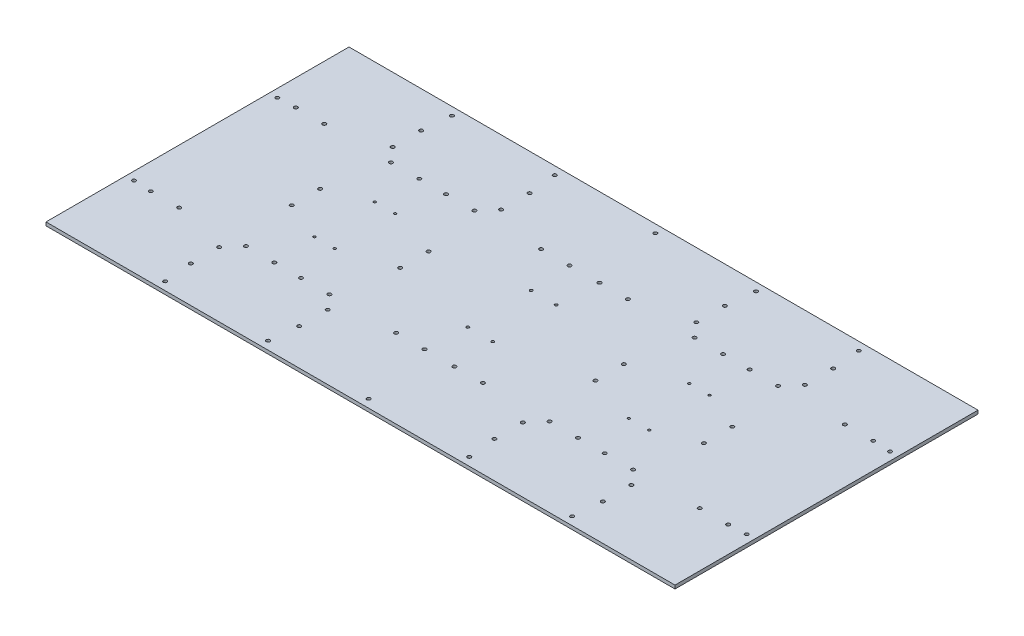
SolidWorks part; units mm, degrees
ref_plane "Front Plane" through (0, 0, 0) normal (0, 0, 1) x (1, 0, 0)
ref_plane "Top Plane" through (0, 0, 0) normal (0, 1, 0) x (1, 0, 0)
ref_plane "Right Plane" through (0, 0, 0) normal (1, 0, 0) x (0, 0, -1)
sketch "Sketch1" plane through (0, 0, 0) normal (0, 1, 0) x (1, 0, 0)
  line L0 (0, 139.7) -> (0, -139.7) construction
  line L1 (-290, 139.7) -> (290, 139.7)
  line L2 (-290, 139.7) -> (-290, -139.7)
  line L3 (-290, -139.7) -> (290, -139.7)
  line L4 (290, 139.7) -> (290, -139.7)
  line L5 (-290, 139.7) -> (290, -139.7) construction
  line L6 (-290, -139.7) -> (290, 139.7) construction
  line L7 (-282.5, 132.2) -> (282.5, 132.2) construction
  line L8 (-282.5, 132.2) -> (-282.5, -132.2) construction
  line L9 (-282.5, -132.2) -> (282.5, -132.2) construction
  line L10 (282.5, 132.2) -> (282.5, -132.2) construction
  line L11 (-282.5, 132.2) -> (282.5, -132.2) construction
  line L12 (-282.5, -132.2) -> (282.5, 132.2) construction
  line L13 (-290, 0) -> (290, 0) construction
  line L14 (282.5, 132.2) -> (282.5, -132.2) construction
  circle A0 centre (-282.5, 66.1) radius 1.65
  circle A1 centre (-187.6333, 132.2) radius 1.65
  circle A2 centre (-92.7667, 132.2) radius 1.65
  circle A3 centre (-282.5, -66.1) radius 1.65
  circle A4 centre (-92.7667, -132.2) radius 1.65
  circle A5 centre (-187.6333, -132.2) radius 1.65
  circle A6 centre (187.6333, -132.2) radius 1.65
  circle A7 centre (92.7667, -132.2) radius 1.65
  circle A8 centre (92.7667, 132.2) radius 1.65
  circle A9 centre (187.6333, 132.2) radius 1.65
  circle A10 centre (282.5, -66.1) radius 1.65
  circle A11 centre (282.5, 66.1) radius 1.65
  circle A12 centre (0, 132.2) radius 1.65
  circle A13 centre (0, -132.2) radius 1.65
  point P0 (0, 0)
  point P6 (0, 0)
  dimension "D5" = 3.3
  dimension "D6" = 3.3
  dimension "D7" = 3.3
  dimension "D12" = 3.3
  dimension "D13" = 3.3
  dimension "D1" = 580
  dimension "D2" = 279.4
  dimension "D3" = 7.5
  dimension "D4" = 7.5
  dimension "D8" = 66.1
  dimension "D9" = 94.8667
  dimension "D10" = 94.8667
  dimension "D11" = 92.7667
extrude "Boss-Extrude1" add sketch "Sketch1" along normal blind 3.175
sketch "Sketch2" plane through (0, 3.175, 0) normal (0, 1, 0) x (1, 0, 0)
  line L0 (0, 139.7) -> (0, -139.7) construction
  line L1 (290, 139.7) -> (-290, 139.7) construction
  line L2 (-290, -139.7) -> (290, -139.7) construction
  line L3 (-140, 139.7) -> (-140, -139.7) construction
  line L5 (-290, 0) -> (290, 0) construction
  line L6 (-290, 139.7) -> (-290, -139.7) construction
  line L7 (290, -139.7) -> (290, 139.7) construction
  line L8 (-190, 139.7) -> (-190, -139.7) construction
  circle A0 centre (-190, 13.1) radius 1.65
  circle A6 centre (-266.2, 66.8739) radius 1.65
  circle A7 centre (-240, 66.8739) radius 1.65
  circle A8 centre (-178.5, 66.8739) radius 1.65
  circle A9 centre (-152.3, 66.8739) radius 1.65
  circle A10 centre (-190, 106.2) radius 1.65
  circle A11 centre (-190, 80) radius 1.65
  circle A12 centre (-190, -80) radius 1.65
  circle A13 centre (-190, -106.2) radius 1.65
  circle A14 centre (-152.3, -66.8739) radius 1.65
  circle A15 centre (-178.5, -66.8739) radius 1.65
  circle A16 centre (-240, -66.8739) radius 1.65
  circle A17 centre (-266.2, -66.8739) radius 1.65
  circle A18 centre (-190, -13.1) radius 1.65
  circle A19 centre (-90, -13.1) radius 1.65
  circle A20 centre (-13.8, -66.8739) radius 1.65
  circle A21 centre (-40, -66.8739) radius 1.65
  circle A22 centre (-101.5, -66.8739) radius 1.65
  circle A23 centre (-127.7, -66.8739) radius 1.65
  circle A24 centre (-90, -106.2) radius 1.65
  circle A25 centre (-90, -80) radius 1.65
  circle A26 centre (-90, 80) radius 1.65
  circle A27 centre (-90, 106.2) radius 1.65
  circle A28 centre (-127.7, 66.8739) radius 1.65
  circle A29 centre (-101.5, 66.8739) radius 1.65
  circle A30 centre (-40, 66.8739) radius 1.65
  circle A31 centre (-13.8, 66.8739) radius 1.65
  circle A32 centre (-90, 13.1) radius 1.65
  circle A33 centre (90, 13.1) radius 1.65
  circle A34 centre (13.8, 66.8739) radius 1.65
  circle A35 centre (40, 66.8739) radius 1.65
  circle A36 centre (101.5, 66.8739) radius 1.65
  circle A37 centre (127.7, 66.8739) radius 1.65
  circle A38 centre (90, 106.2) radius 1.65
  circle A39 centre (90, 80) radius 1.65
  circle A40 centre (90, -80) radius 1.65
  circle A41 centre (90, -106.2) radius 1.65
  circle A42 centre (127.7, -66.8739) radius 1.65
  circle A43 centre (101.5, -66.8739) radius 1.65
  circle A44 centre (40, -66.8739) radius 1.65
  circle A45 centre (13.8, -66.8739) radius 1.65
  circle A46 centre (90, -13.1) radius 1.65
  circle A47 centre (190, -13.1) radius 1.65
  circle A48 centre (266.2, -66.8739) radius 1.65
  circle A49 centre (240, -66.8739) radius 1.65
  circle A50 centre (178.5, -66.8739) radius 1.65
  circle A51 centre (152.3, -66.8739) radius 1.65
  circle A52 centre (190, -106.2) radius 1.65
  circle A53 centre (190, -80) radius 1.65
  circle A54 centre (190, 80) radius 1.65
  circle A55 centre (190, 106.2) radius 1.65
  circle A56 centre (152.3, 66.8739) radius 1.65
  circle A57 centre (178.5, 66.8739) radius 1.65
  circle A58 centre (240, 66.8739) radius 1.65
  circle A59 centre (266.2, 66.8739) radius 1.65
  circle A60 centre (190, 13.1) radius 1.65
  dimension "D6" = 3.3
  dimension "D4" = 13.1
  dimension "D10" = 26.2
  dimension "D11" = 26.2
  dimension "D14" = 26.2
  dimension "D15" = 11.5
  dimension "D3" = 190
  dimension "D16" = 50
  dimension "D17" = 80
  dimension "D18" = 50
  dimension "D19" = 66.8739
extrude "Cut-Extrude1" cut sketch "Sketch2" against normal up to surface (3.175 mm away) up to face at (0, 0, 0)
sketch "Sketch3" plane through (0, 3.175, 0) normal (0, 1, 0) x (1, 0, 0)
  line L1 (-11.525, 29.25) -> (11.525, 29.25) construction
  line L2 (-11.525, 29.25) -> (-11.525, -29.25) construction
  line L3 (-11.525, -29.25) -> (11.525, -29.25) construction
  line L4 (11.525, 29.25) -> (11.525, -29.25) construction
  line L5 (-11.525, 29.25) -> (11.525, -29.25) construction
  line L6 (-11.525, -29.25) -> (11.525, 29.25) construction
  line L7 (-145, 139.7) -> (-145, -139.7) construction
  line L8 (290, 139.7) -> (-290, 139.7) construction
  line L9 (-290, -139.7) -> (290, -139.7) construction
  line L10 (0, 139.7) -> (0, -139.7) construction
  line L11 (-290, 139.7) -> (-290, -139.7) construction
  line L12 (154.35, -27.85) -> (135.65, 27.85) construction
  line L13 (-154.35, 27.85) -> (-135.65, 27.85) construction
  line L14 (-154.35, 27.85) -> (-154.35, -27.85) construction
  line L15 (-154.35, -27.85) -> (-135.65, -27.85) construction
  line L16 (-135.65, 27.85) -> (-135.65, -27.85) construction
  line L17 (-154.35, 27.85) -> (-135.65, -27.85) construction
  line L18 (-154.35, -27.85) -> (-135.65, 27.85) construction
  line L19 (154.35, 27.85) -> (135.65, -27.85) construction
  line L20 (135.65, 27.85) -> (135.65, -27.85) construction
  line L21 (154.35, -27.85) -> (135.65, -27.85) construction
  line L22 (154.35, 27.85) -> (154.35, -27.85) construction
  line L23 (154.35, 27.85) -> (135.65, 27.85) construction
  line L24 (145, 139.7) -> (145, -139.7) construction
  circle A0 centre (-11.525, 29.25) radius 1.3
  circle A1 centre (11.525, 29.25) radius 1.3
  circle A2 centre (11.525, -29.25) radius 1.3
  circle A3 centre (-11.525, -29.25) radius 1.3
  circle A4 centre (-154.35, 27.85) radius 1.1
  circle A5 centre (-135.65, 27.85) radius 1.1
  circle A6 centre (-135.65, -27.85) radius 1.1
  circle A7 centre (-154.35, -27.85) radius 1.1
  circle A8 centre (154.35, -27.85) radius 1.1
  circle A9 centre (135.65, -27.85) radius 1.1
  circle A10 centre (135.65, 27.85) radius 1.1
  circle A11 centre (154.35, 27.85) radius 1.1
  point P0 (0, 0)
  point P20 (-145, 0)
  point P39 (145, 0)
  dimension "D1" = 2.6
  dimension "D6" = 2.2
  dimension "D2" = 58.5
  dimension "D3" = 23.05
  dimension "D4" = 290
  dimension "D5" = 145
  dimension "D7" = 55.7
  dimension "D8" = 18.7
extrude "Cut-Extrude2" cut sketch "Sketch3" against normal up to surface (3.175 mm away) up to face at (-101.5, 0, 68.5239)
equation "\"D6@Sketch1\"=\"D5@Sketch1\""
equation "\"D7@Sketch1\"=\"D5@Sketch1\""
equation "\"D10@Sketch1\"=\"D9@Sketch1\""
equation "\"D12@Sketch1\"=\"D5@Sketch1\""
equation "\"D13@Sketch1\"=\"D5@Sketch1\""
equation "\"D11@Sketch2\"=\"D10@Sketch2\""
equation "\"D4@Sketch2\"=\"D10@Sketch2\"/2"
equation "\"D14@Sketch2\"=\"D10@Sketch2\""
equation "\"D5@Sketch3\"=\"D4@Sketch3\"/2"
